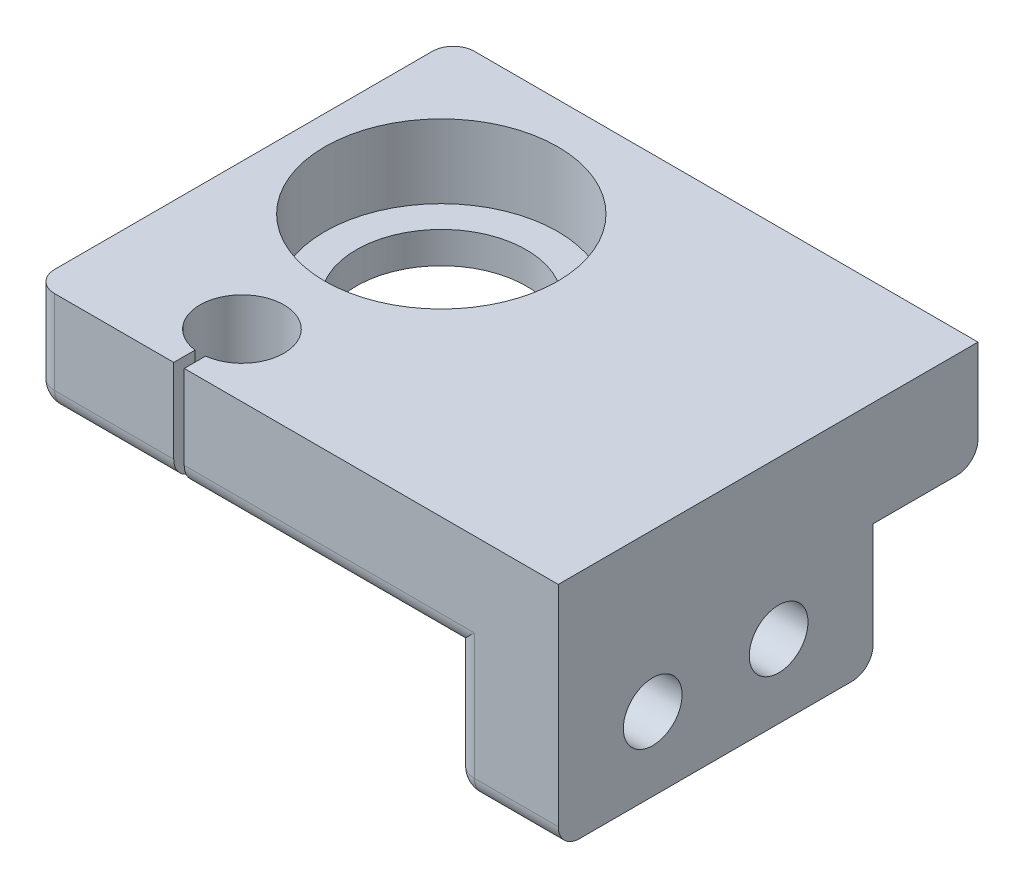
SolidWorks part; units mm, degrees
ref_plane "Front Plane" through (0, 0, 0) normal (0, 0, 1) x (1, 0, 0)
ref_plane "Top Plane" through (0, 0, 0) normal (0, 1, 0) x (1, 0, 0)
ref_plane "Right Plane" through (0, 0, 0) normal (1, 0, 0) x (0, 0, -1)
sketch "Sketch1" plane through (0, 0, 0) normal (0, 1, 0) x (1, 0, 0)
  line L0 (13.85, -15) -> (13.85, -34) construction
  line L1 (0, 0) -> (50, 0)
  line L2 (0, 0) -> (0, -40)
  line L3 (0, -40) -> (50, -40)
  line L4 (50, 0) -> (50, -40)
  line L5 (13.85, -34) -> (13.85, -40) construction
  line L6 (13.85, -15) -> (13.85, 0) construction
  line L8 (13.35, -37.9686) -> (14.35, -37.9686)
  line L9 (13.35, -37.9686) -> (13.35, -40)
  line L10 (13.35, -40) -> (14.35, -40)
  line L11 (14.35, -37.9686) -> (14.35, -40)
  circle A0 centre (13.85, -34) radius 4
  circle A1 centre (13.85, -15) radius 8.1
  circle A2 centre (13.85, -15) radius 11.1 construction
  dimension "D3" = 8
  dimension "D4" = 6
  dimension "D6" = 22.2
  dimension "D7" = 3
  dimension "D1" = 40
  dimension "D2" = 50
  dimension "D5" = 19
  dimension "D8" = 1
  dimension "D9" = 13.85
extrude "Boss-Extrude1" add sketch "Sketch1" along normal blind 10 contours A0 L1 L2 L3 L4 A1 region at (26.6543, 0, 20.1658)
sketch "Sketch2" plane through (0, 10, 0) normal (0, 1, 0) x (1, 0, 0)
  circle A0 centre (13.85, -15) radius 11.1 construction
  circle A1 centre (13.85, -15) radius 11.1
extrude "Cut-Extrude1" cut sketch "Sketch2" against normal blind 7
sketch "Sketch6" plane through (0, 0, 40) normal (0, 0, 1) x (1, 0, 0)
  line L1 (50, 0) -> (40, 0)
  line L2 (50, 0) -> (50, -12)
  line L3 (50, -12) -> (40, -12)
  line L4 (40, 0) -> (40, -12)
  dimension "D1" = 12
  dimension "D2" = 10
extrude "Boss-Extrude3" add sketch "Sketch6" against normal blind 30
sketch "Sketch7" plane through (40, 0, 0) normal (-1, 0, 0) x (0, 0, 1)
  line L0 (31, -5) -> (19, -5) construction
  line L1 (19, -5) -> (10, -5) construction
  line L2 (10, 0) -> (10, -12) construction
  line L3 (31, -5) -> (40, -5) construction
  line L4 (40, 0) -> (40, -12) construction
  line L5 (10, 0) -> (40, 0) construction
  circle A0 centre (19, -5) radius 2.8
  circle A1 centre (31, -5) radius 2.8
  dimension "D1" = 12
  dimension "D3" = 5.6
  dimension "D2" = 5
extrude "Cut-Extrude2" cut sketch "Sketch7" against normal through all
sketch "Sketch8" plane through (40, 0, 0) normal (-1, 0, 0) x (0, 0, 1)
  circle A0 centre (19, -5) radius 4.3
  circle A1 centre (31, -5) radius 4.3
  dimension "D1" = 8.6
extrude "Cut-Extrude3" cut sketch "Sketch8" against normal blind 6
fillet "Fillet1" radius 2 11 edges at (45, -12, 10) (45, -12, 40) (6.675, 0, 40) (27.175, 0, 40) (40, -6, 40) (40, -12, 25) (40, -6, 10) (0, 5, 40) (0, 5, 0) (25, 0, 0) (0, 0, 20)
